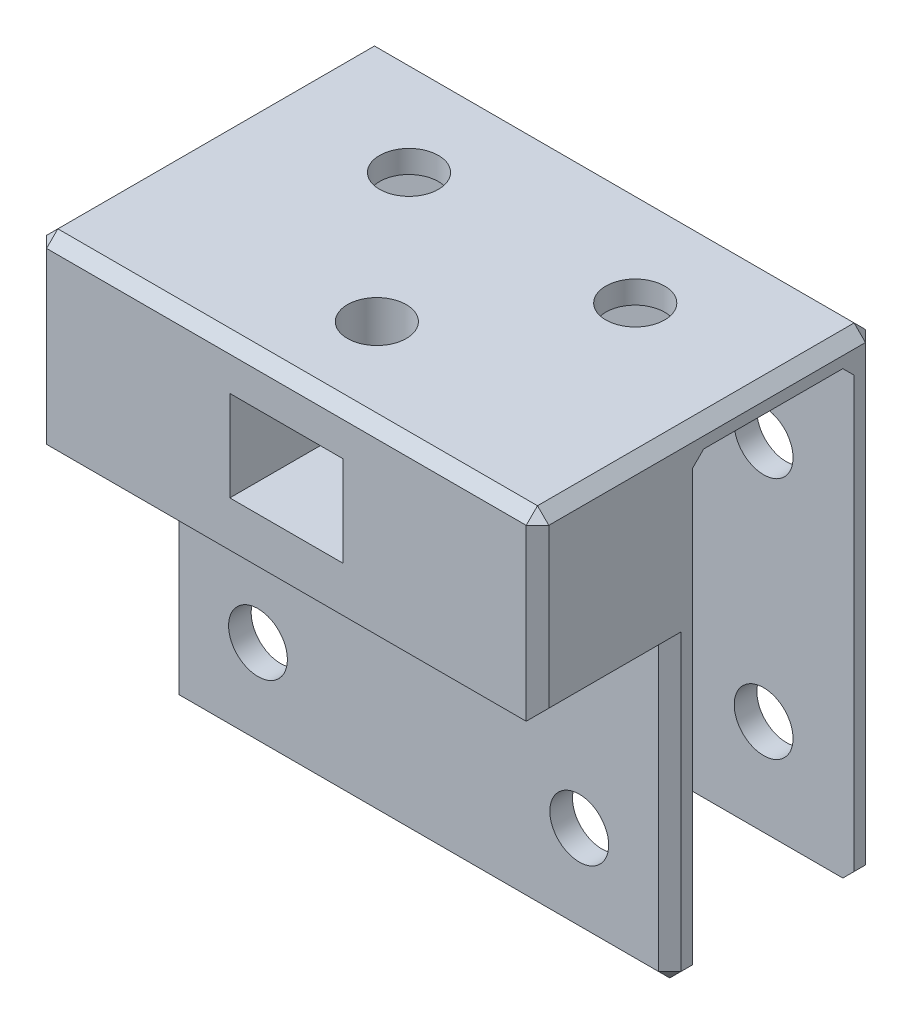
SolidWorks part; units mm, degrees
ref_plane "Front Plane" through (0, 0, 0) normal (0, 0, 1) x (1, 0, 0)
ref_plane "Top Plane" through (0, 0, 0) normal (0, 1, 0) x (1, 0, 0)
ref_plane "Right Plane" through (0, 0, 0) normal (1, 0, 0) x (0, 0, -1)
sketch "Sketch1" plane through (0, 0, 0) normal (0, 0, 1) x (1, 0, 0)
  line L0 (22.2, 40) -> (22.2, 0) construction
  line L1 (0, 0) -> (44.4, 0)
  line L2 (0, 0) -> (0, 40)
  line L3 (0, 40) -> (44.4, 40)
  line L4 (44.4, 0) -> (44.4, 40)
  line L5 (0, 0) -> (8, 0) construction
  line L6 (0, 0) -> (0, 8) construction
  line L10 (8, 29.9769) -> (8, 27.3769) construction
  line L11 (8, 19) -> (8, 8.4769) construction
  line L12 (8, 19) -> (10.573, 19) construction
  line L15 (10.573, 19) -> (10.573, 40) construction
  line L16 (8, 8.4769) -> (36.4, 8.4769) construction
  line L17 (36.4, 8.4769) -> (36.4, 29.9769) construction
  circle A0 centre (8, 8.4769) radius 2.6
  circle A1 centre (8, 29.9769) radius 2.6
  circle A2 centre (36.4, 29.9769) radius 2.6
  circle A3 centre (36.4, 8.4769) radius 2.6
  dimension "D5" = 5.2
  dimension "D6" = 5.2
  dimension "D7" = 5.2
  dimension "D8" = 5.2
  dimension "D1" = 44.4
  dimension "D2" = 40
  dimension "D3" = 21.5
  dimension "D4" = 21.5
  dimension "D9" = 21
  dimension "D10" = 8
  dimension "D11" = 8
extrude "Boss-Extrude1" add sketch "Sketch1" along normal blind 2
sketch "Sketch2" plane through (0, 40, 0) normal (0, 1, 0) x (1, 0, 0)
  line L0 (44.4, -2) -> (44.4, 0) construction
  line L1 (0, -2) -> (44.4, -2)
  line L2 (0, -2) -> (0, 16.3)
  line L3 (0, 16.3) -> (44.4, 16.3)
  line L4 (44.4, -2) -> (44.4, 16.3)
  dimension "D1" = 18.3
  dimension "D2" = 44.4
extrude "Boss-Extrude2" add sketch "Sketch2" along normal blind 2
pattern_linear "LPattern1" count 2 spacing 16.3 along (0, 0, -1) of "Boss-Extrude1"
sketch "Sketch3" plane through (0, 42, 0) normal (0, 1, 0) x (1, 0, 0)
  line L0 (22.2, 16.3) -> (22.2, -2) construction
  line L1 (44.4, 16.3) -> (0, 16.3) construction
  line L2 (0, -2) -> (44.4, -2) construction
  line L3 (22.2, 7.15) -> (12.2, 7.15) construction
  line L4 (22.2, 7.15) -> (32.2, 7.15) construction
  circle A0 centre (12.2, 7.15) radius 2.6
  circle A1 centre (32.2, 7.15) radius 2.6
  dimension "D3" = 5.2
  dimension "D4" = 5.2
  dimension "D1" = 10
  dimension "D2" = 10
extrude "Cut-Extrude1" cut sketch "Sketch3" against normal through all
sketch "Sketch5" plane through (0, 0, -16.3) normal (0, 0, -1) x (-1, 0, 0)
  line L1 (-22.2, 41) -> (-22.2, 34.93) construction
  dimension "D1" = 6.07
ref_plane "Plane1" through (22.2, 0, 0) normal (1, 0, 0) x (0, 0, -1)
sketch "Sketch6" plane through (22.2, 0, 0) normal (1, 0, 0) x (0, 0, -1)
  line L0 (16.3, 42) -> (-2, 42) construction
  line L1 (16.3, 41) -> (16.3, 34.93) construction
  line L3 (-2, 42) -> (-13.69, 42)
  line L4 (-13.69, 42) -> (-13.69, 26)
  line L5 (-13.69, 26) -> (-2, 26)
  line L6 (-2, 26) -> (-2, 42)
  dimension "D1" = 11.69
  dimension "D2" = 16
extrude "Boss-Extrude3" add sketch "Sketch6" along normal up to surface (22.2 mm away) and the other way up to surface (22.2 mm away) up to face at (44.4, 20.5, -7.15) other way up to face at (0, 20.5, -7.15)
fillet "Fillet4" radius 1 20 edges at (22.2, 40, -14.3) (22.2, 40, 0) (22.2, 42, -16.3) (0, 42, -1.305) (44.4, 42, -1.305) (44.4, 13, 2) (44.4, 21, -16.3) (0, 21, -16.3) (0, 13, 2) (44.4, 0, 1) (0, 0, 1) (0, 0, -15.3) (44.4, 0, -15.3) (22.2, 0, -16.3) (22.2, 0, 2) (22.2, 42, 13.69) (44.4, 26, 7.845) (44.4, 34, 13.69) (0, 26, 7.845) (0, 34, 13.69) profile chamfer
sketch "Sketch11" plane through (0, 42, 0) normal (0, 1, 0) x (1, 0, 0)
  line L0 (22.2, -13.69) -> (22.2, -5.69) construction
  line L5 (43.4, -13.69) -> (1, -13.69) construction
  circle A0 centre (22.2, -5.69) radius 2.6
  dimension "D2" = 5.2
  dimension "D1" = 8
sketch "Sketch12" plane through (0, 26, 0) normal (0, -1, 0) x (1, 0, 0)
  line L1 (3, 2) -> (13, 2)
  line L2 (3, 2) -> (3, 10.3844)
  line L3 (3, 10.3844) -> (13, 10.3844)
  line L4 (41.4, 2) -> (41.4, 10.3844)
  line L6 (1, 13.69) -> (1, 2) construction
  line L7 (31.4, 10.3844) -> (31.4, 2)
  line L10 (43.4, 2) -> (43.4, 13.69) construction
  line L11 (3, 10.3844) -> (13, 10.3844)
  line L12 (3, 10.3844) -> (3, 2)
  line L13 (3, 2) -> (13, 2)
  line L14 (13, 10.3844) -> (13, 2)
  line L15 (31.4, 10.3844) -> (41.4, 10.3844)
  line L16 (31.4, 2) -> (41.4, 2)
  line L17 (43.4, 2) -> (1, 2) construction
  line M8 (1, 2) -> (43.4, 2)
  line M12 (1, 2) -> (43.4, 2)
  line M14 (1, 2) -> (43.4, 2)
  dimension "D1" = 2
  dimension "D2" = 2
  dimension "D4" = 10
  dimension "D5" = 10
extrude "Cut-Extrude7" cut sketch "Sketch12" against normal offset from surface (11 mm away) 5 contours L14 L3 L2 M12 M14 | L15 L7 L4 M14 M8 region at (8, 26, 6.1922) region at (36.4, 26, 6.1922) up to face at (22.2, 42, -1.305)
extrude "Cut-Extrude8" cut sketch "Sketch11" against normal blind 10
sketch "Sketch13" plane through (0, 0, 13.69) normal (0, 0, 1) x (1, 0, 0)
  line L0 (22.2, 42) -> (22.2, 34) construction
  line L1 (1, 42) -> (43.4, 42) construction
  line L2 (27.2, 38) -> (17.2, 38)
  line L3 (27.2, 38) -> (27.2, 30)
  line L4 (17.2, 38) -> (17.2, 30)
  line L5 (27.2, 30) -> (17.2, 30)
  line L6 (17.2, 34) -> (27.2, 34) construction
  line L7 (22.2, 38) -> (22.2, 30) construction
  dimension "D1" = 8
  dimension "D2" = 8
  dimension "D3" = 10
extrude "Cut-Extrude9" cut sketch "Sketch13" against normal up to surface (11.69 mm away) up to face at (22.2, 25.5, 2)
